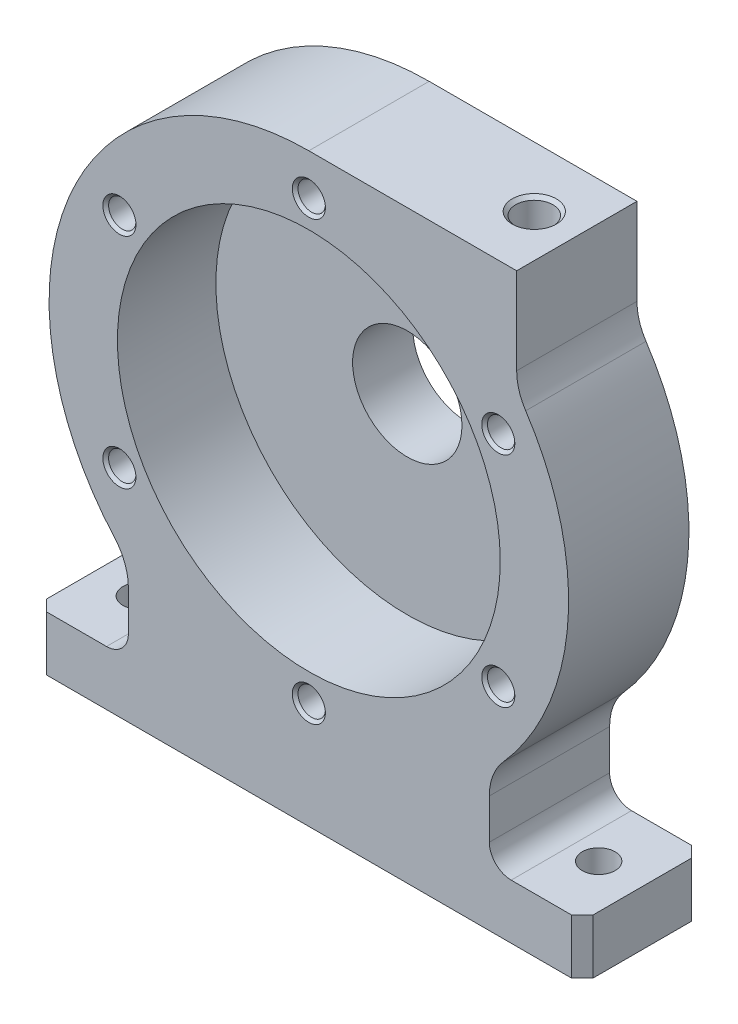
SolidWorks part; units mm, degrees
material "Cast Alloy Steel"
ref_plane "Front Plane" through (0, 0, 0) normal (0, 0, 1) x (1, 0, 0)
ref_plane "Top Plane" through (0, 0, 0) normal (0, 1, 0) x (1, 0, 0)
ref_plane "Right Plane" through (0, 0, 0) normal (1, 0, 0) x (0, 0, -1)
sketch "Sketch1" plane through (0, 0, 0) normal (0, 0, 1) x (1, 0, 0)
  line L0 (0, 47.5) -> (38, 47.5)
  line L1 (0, 60.6729) -> (0, -59.5) construction
  line L2 (38, 47.5) -> (38, 31.6583)
  line L3 (38, 60.6729) -> (38, -53.7791) construction
  line L4 (-50, -59.5) -> (50, -59.5)
  line L5 (-50, -49.5) -> (-37, -49.5)
  line L6 (-50, -49.5) -> (-50, -59.5)
  line L7 (50, -49.5) -> (50, -59.5)
  line L8 (-50, 60.6729) -> (-50, -53.7791) construction
  line L9 (0, 60.6729) -> (0, -53.7791) construction
  line L10 (50, 60.6729) -> (50, -53.7791) construction
  line L11 (-69.8786, -49.5) -> (69.1975, -49.5) construction
  line L12 (-69.8786, -59.5) -> (69.1975, -59.5) construction
  line L13 (-33, -38.1739) -> (-33, -45.5)
  line L14 (37, -49.5) -> (50, -49.5)
  line L15 (-33, 60.6729) -> (-33, -59.5) construction
  line L16 (33, -38.1739) -> (33, -45.5)
  arc A0 (0, 47.5) -> (-35.5217, -31.535) centre (0, 0) ccw
  arc A1 (35.5217, -31.535) -> (39.6522, 26.1525) centre (0, 0) ccw
  arc A2 (35.5217, -31.535) -> (33, -38.1739) centre (43, -38.1739) ccw
  arc A3 (-33, -38.1739) -> (-35.5217, -31.535) centre (-43, -38.1739) ccw
  arc A4 (37, -49.5) -> (33, -45.5) centre (37, -45.5) cw
  arc A5 (-33, -45.5) -> (-37, -49.5) centre (-37, -45.5) cw
  arc A6 (39.6522, 26.1525) -> (38, 31.6583) centre (48, 31.6583) cw
  point P30 (33, -34.165)
  dimension "D1" = 95
  dimension "D9" = 10
  dimension "D10" = 4
  dimension "D11" = 10
  dimension "D3" = 59.5
  dimension "D4" = 10
  dimension "D8" = 33
  dimension "D2" = 38
  dimension "D5" = 50
  dimension "D6" = 50
  dimension "D7" = 33
extrude "Boss-Extrude1" add sketch "Sketch1" along normal mid plane 22
sketch "Sketch2" plane through (0, 0, 11) normal (0, 0, 1) x (1, 0, 0)
  circle A0 centre (0, 0) radius 35
  dimension "D1" = 70
extrude "Cut-Extrude1" cut sketch "Sketch2" against normal blind 18
sketch "Sketch4" plane through (0, 0, -11) normal (0, 0, -1) x (-1, 0, 0)
  circle A0 centre (0, 0) radius 10
  circle A1 centre (0, 0) radius 14
  dimension "D1" = 20
  dimension "D2" = 28
extrude "Boss-Extrude2" add sketch "Sketch4" along normal blind 7
sketch "Sketch5" plane through (0, 0, -11) normal (0, 0, -1) x (-1, 0, 0)
  circle A0 centre (0, 0) radius 10
  dimension "D1" = 20
extrude "Cut-Extrude2" cut sketch "Sketch5" against normal through all
fillet "Fillet1" radius 4 1 edges at (-14, 0, -11)
chamfer "Chamfer1" distance 2 angle 45 4 edges at (50, -54.5, -11) (50, -54.5, 11) (-50, -54.5, -11) (-50, -54.5, 11)
sketch "Sketch6" plane through (0, 47.5, 0) normal (0, 1, 0) x (1, 0, 0)
  line L0 (0, 0) -> (38, 0) construction
  line L1 (38, -11) -> (38, 11) construction
hole_wizard "M8x1.25 Tapped Hole1" positions "Sketch7" profile "Sketch8" tap size "M8x1.25" standard "ANSI Metric"
sketch "Sketch7" plane through (0, 47.5, 0) normal (0, 1, 0) x (1, 0, 0)
  line L0 (0, 0) -> (38, 0) construction
  line L1 (38, -11) -> (38, 11) construction
  point P0 (30.2241, 0)
  dimension "D1" = 7.7759
sketch "Sketch8" plane through (30.2241, 47.5, 0) normal (1, 0, 0) x (0, 0, 1)
  line L0 (0, 0) -> (0, 31.7929)
  line L1 (0, 31.7929) -> (3.4, 29.75)
  line L2 (3.4, 29.75) -> (3.4, 0.625)
  line L3 (3.4, 0.625) -> (4.025, 0)
  line L5 (4.025, 0) -> (0, 0)
  line L6 (-3.4, 0.625) -> (-4.025, 0) construction
  line L10 (0, 31.7929) -> (-3.4, 29.75) construction
  line L11 (0, -6.35) -> (0, 107.95) construction
  dimension "Tap Drill Dia." = 6.8
  dimension "Tap Drill Depth" = 29.75
  dimension "Near C'Sink Dia." = 8.05
  dimension "Near C'Sink Angle" = 90
  dimension "Drill Angle" = 118
cosmetic thread "Hole Thread1" parameters "D1"=16, "D2"=8
sketch "Sketch9" plane through (0, 0, 11) normal (0, 0, 1) x (1, 0, 0)
  circle A0 centre (0, 0) radius 40 construction
  dimension "D1" = 80
hole_wizard "M6x1.0 Tapped Hole1" positions "Sketch10" profile "Sketch11" tap size "M6x1.0" standard "ANSI Metric"
sketch "Sketch10" plane through (0, 0, 11) normal (0, 0, 1) x (1, 0, 0)
  circle A0 centre (0, 0) radius 40 construction
  point P0 (0, 40)
sketch "Sketch11" plane through (0, 40, 11) normal (1, 0, 0) x (0, -1, 0)
  line L0 (0, 0) -> (0, 16.5022)
  line L1 (0, 16.5022) -> (2.5, 15)
  line L2 (2.5, 15) -> (2.5, 0.525)
  line L3 (2.5, 0.525) -> (3.025, 0)
  line L5 (3.025, 0) -> (0, 0)
  line L6 (-2.5, 0.525) -> (-3.025, 0) construction
  line L10 (0, 16.5022) -> (-2.5, 15) construction
  line L11 (0, -6.35) -> (0, 107.95) construction
  dimension "Tap Drill Dia." = 5
  dimension "Tap Drill Depth" = 15
  dimension "Near C'Sink Dia." = 6.05
  dimension "Near C'Sink Angle" = 90
  dimension "Drill Angle" = 118
cosmetic thread "Hole Thread2" parameters "D1"=12, "D2"=6
pattern_circular "CirPattern1" count 6 over 360 about axis through (0, 0, -7) along (0, 0, 1) of "M6x1.0 Tapped Hole1"
cosmetic thread "Hole Thread3" parameters "D1"=12, "D2"=6
cosmetic thread "Hole Thread4" parameters "D1"=12, "D2"=6
cosmetic thread "Hole Thread5" parameters "D1"=12, "D2"=6
cosmetic thread "Hole Thread6" parameters "D1"=12, "D2"=6
cosmetic thread "Hole Thread7" parameters "D1"=12, "D2"=6
hole_wizard "CSK for M8 Countersunk Flat Head Screw1" positions "Sketch12" profile "Sketch13" countersink size "M8" standard "ISO"
sketch "Sketch12" plane through (0, -59.5, 0) normal (0, -1, 0) x (-1, 0, 0)
  line L0 (-50, -9) -> (-50, 9) construction
  line L1 (50, -9) -> (50, 9) construction
  point P0 (-42, 0)
  point P2 (42, 0)
  dimension "D1" = 8
  dimension "D2" = 8
sketch "Sketch13" plane through (42, -59.5, 0) normal (1, 0, 0) x (0, 0, -1)
  line L0 (0, 0) -> (0, 21.8026)
  line L1 (0, 21.8026) -> (3, 20)
  line L2 (3, 20) -> (3, 1)
  line L3 (3, 1) -> (4, 0)
  line L5 (4, 0) -> (0, 0)
  line L6 (-3, 1) -> (-4, 0) construction
  line L10 (0, 21.8026) -> (-3, 20) construction
  line L11 (0, -6.35) -> (0, 107.95) construction
  dimension "Hole Dia." = 6
  dimension "Hole Depth" = 20
  dimension "Near C'Sink Dia." = 8
  dimension "Near C'Sink Angle" = 90
  dimension "Drill Angle" = 118
